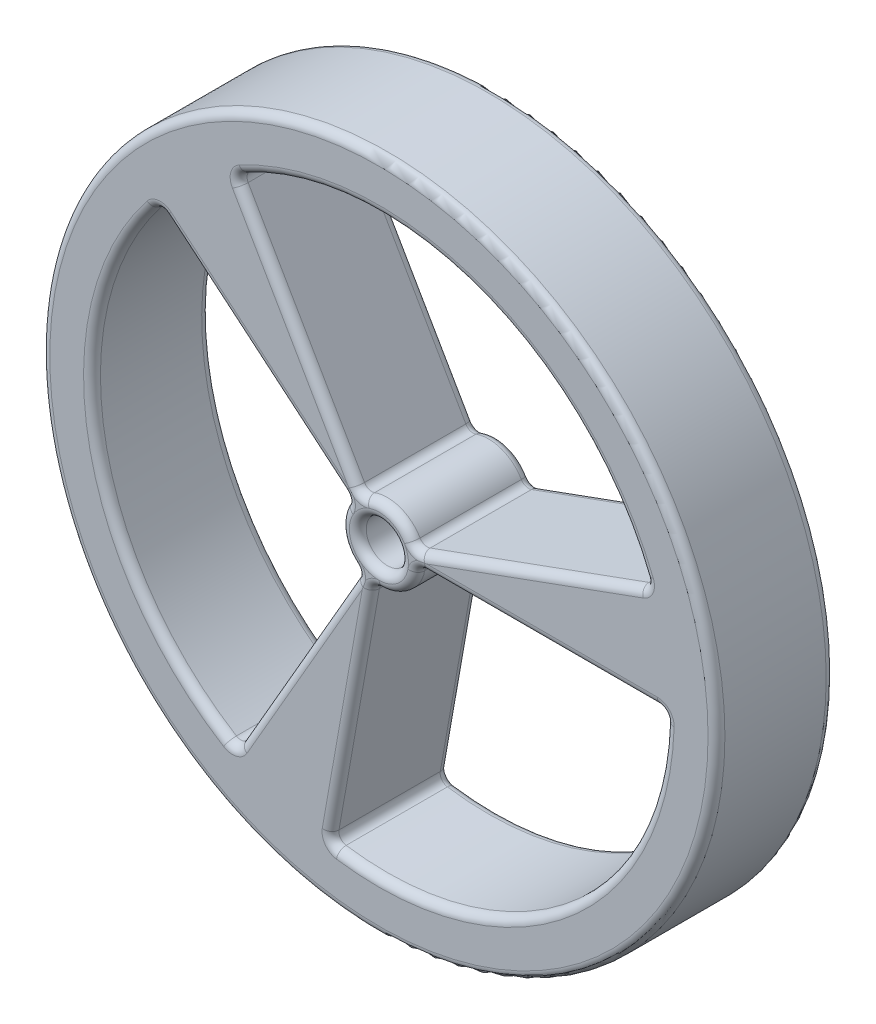
SolidWorks part; units mm, degrees
ref_plane "Front Plane" through (0, 0, 0) normal (0, 0, 1) x (1, 0, 0)
ref_plane "Top Plane" through (0, 0, 0) normal (0, 1, 0) x (1, 0, 0)
ref_plane "Right Plane" through (0, 0, 0) normal (1, 0, 0) x (0, 0, -1)
sketch "Sketch1" plane through (0, 0, 0) normal (0, 0, 1) x (1, 0, 0)
  line L0 (2.25, 0) -> (17, 0)
  line L1 (2.1143, 0.7695) -> (15.9748, 5.8143)
  line L2 (-0.3907, -2.2158) -> (-2.952, -16.7417)
  line L3 (-1.125, -1.9486) -> (-8.5, -14.7224)
  line L4 (-22.4149, 0) -> (24.9918, 0) construction
  line L5 (-1.7236, 1.4463) -> (-13.0228, 10.9274)
  line L6 (-1.125, 1.9486) -> (-8.5, 14.7224)
  arc A0 (-13.0228, 10.9274) -> (-8.5, -14.7224) centre (0, 0) ccw
  arc A1 (-1.7236, 1.4463) -> (-1.125, -1.9486) centre (0, 0) ccw
  circle A2 centre (0, 0) radius 1.25
  circle A3 centre (0, 0) radius 20
  arc A4 (-2.952, -16.7417) -> (17, 0) centre (0, 0) ccw
  arc A5 (15.9748, 5.8143) -> (-8.5, 14.7224) centre (0, 0) ccw
  arc A6 (2.1143, 0.7695) -> (-1.125, 1.9486) centre (0, 0) ccw
  arc A7 (-0.3907, -2.2158) -> (2.25, 0) centre (0, 0) ccw
  point P23 (0, 0)
  dimension "D1" = 2.5
  dimension "D2" = 1
  dimension "D3" = 40
  dimension "D4" = 3
  dimension "D5" = 20
  dimension "D6" = 3
extrude "Boss-Extrude1" add sketch "Sketch1" along normal blind 7
fillet "Fillet1" radius 0.5 40 edges at (1.4463, -1.7236, 7) (1.4463, -1.7236, 0) (10.9274, -13.0228, 7) (10.9274, -13.0228, 0) (-2.2158, -0.3907, 7) (-2.2158, -0.3907, 0) (-16.7417, -2.952, 7) (-16.7417, -2.952, 0) (5.8143, 15.9748, 7) (5.8143, 15.9748, 0) (0.7695, 2.1143, 7) (0.7695, 2.1143, 0) (1.25, 0, 0) (1.25, 0, 7) (20, 0, 0) (20, 0, 7) (-2.952, -16.7417, 3.5) (-1.6714, -9.4788, 7) (-0.3907, -2.2158, 3.5) (-1.6714, -9.4788, 0) (2.25, 0, 3.5) (9.625, 0, 7) (17, 0, 3.5) (9.625, 0, 0) (-13.0228, 10.9274, 3.5) (-7.3732, 6.1868, 7) (-1.7236, 1.4463, 3.5) (-7.3732, 6.1868, 0) (-1.125, 1.9486, 3.5) (-4.8125, 8.3355, 7) (-8.5, 14.7224, 3.5) (-4.8125, 8.3355, 0) (-1.125, -1.9486, 3.5) (-4.8125, -8.3355, 7) (-8.5, -14.7224, 3.5) (-4.8125, -8.3355, 0) (15.9748, 5.8143, 3.5) (9.0445, 3.2919, 7) (2.1143, 0.7695, 3.5) (9.0445, 3.2919, 0)
